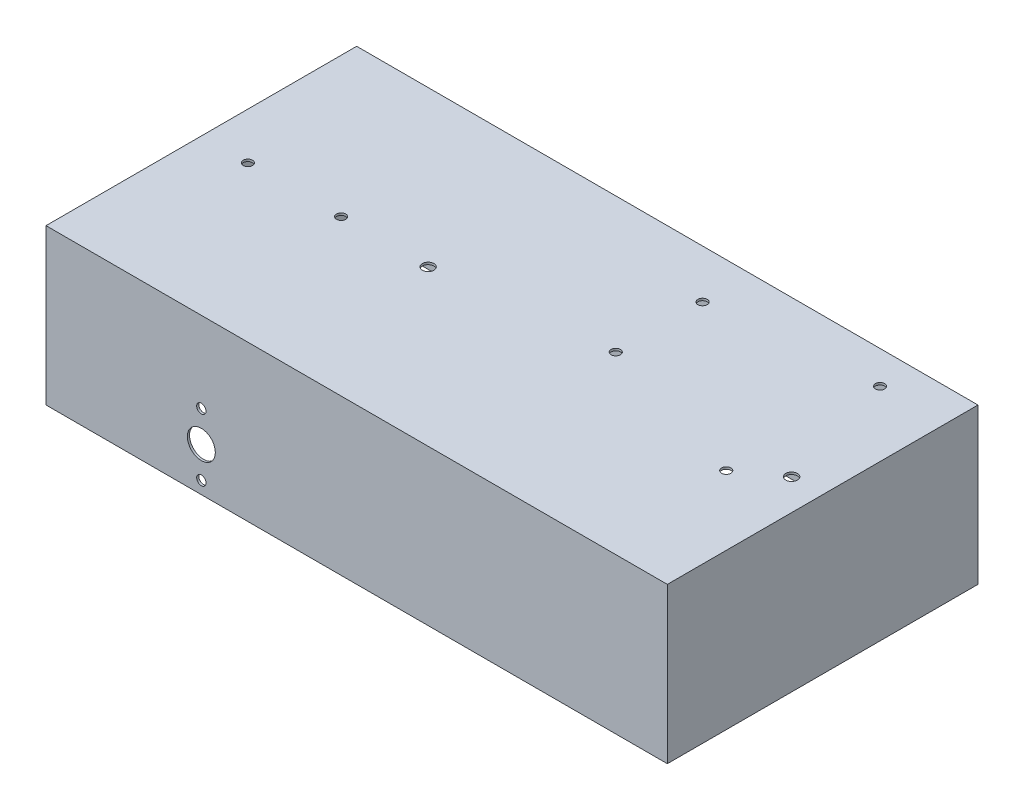
SolidWorks part; units mm, degrees
ref_plane "Front Plane" through (0, 0, 0) normal (0, 0, 1) x (1, 0, 0)
ref_plane "Top Plane" through (0, 0, 0) normal (0, 1, 0) x (1, 0, 0)
ref_plane "Right Plane" through (0, 0, 0) normal (1, 0, 0) x (0, 0, -1)
sketch "Sketch1" plane through (0, 0, 0) normal (0, 1, 0) x (1, 0, 0)
  line L1 (0, 50) -> (200, 50)
  line L2 (0, 50) -> (0, -50)
  line L3 (0, -50) -> (200, -50)
  line L4 (200, 50) -> (200, -50)
  point P4 (0, 0)
  dimension "D1" = 200
  dimension "D2" = 100
extrude "Boss-Extrude1" add sketch "Sketch1" along normal blind 50
sketch "Sketch2" plane through (0, 0, 50) normal (0, 0, 1) x (1, 0, 0)
  line L0 (0, 50) -> (0, 0) construction
  line L1 (50, 24) -> (50, 4) construction
  line L2 (0, 50) -> (200, 50) construction
  circle A0 centre (50, 14) radius 4.5
  circle A1 centre (50, 4) radius 1.5
  circle A2 centre (50, 24) radius 1.5
  point P0 (50, 14)
  point P9 (50, 14)
  dimension "D3" = 9
  dimension "D4" = 3
  dimension "D1" = 50
  dimension "D2" = 36
  dimension "D5" = 20
sketch "Sketch3" plane through (0, 0, 0) normal (0, -1, 0) x (1, 0, 0)
  line L0 (0.7, 49.3) -> (0.7, -49.3)
  line L1 (0.7, -49.3) -> (199.3, -49.3)
  line L2 (199.3, -49.3) -> (199.3, 49.3)
  line L3 (199.3, 49.3) -> (0.7, 49.3)
  line L4 (0, 50) -> (0, -50)
  line L5 (0, -50) -> (200, -50)
  line L6 (200, -50) -> (200, 50)
  line L7 (200, 50) -> (0, 50)
  line L8 (0, 50) -> (0, -50) construction
  line L9 (0, -50) -> (200, -50) construction
  line L10 (200, -50) -> (200, 50) construction
  line L11 (200, 50) -> (0, 50) construction
  dimension "D1" = 0
  dimension "D2" = 0.7
extrude "Cut-Extrude1" cut sketch "Sketch3" against normal offset from surface (49.3 mm away) 0.7 up to face at (100, 50, 0)
sketch "Sketch4" plane through (0, 0, 0) normal (0, -1, 0) x (1, 0, 0)
  line L0 (0.7, -49.3) -> (199.3, -49.3) construction
  line L1 (145, -49.3) -> (199.3, -49.3)
  line L2 (145, -49.3) -> (145, 49.3)
  line L3 (145, 49.3) -> (199.3, 49.3)
  line L4 (199.3, -49.3) -> (199.3, 49.3)
  line L5 (199.3, 49.3) -> (0.7, 49.3) construction
  line L6 (160, -47.9) -> (160, 49.3) construction
  line L7 (200, -50) -> (200, 50) construction
  line L8 (199.3, -49.3) -> (199.3, 49.3) construction
  circle A0 centre (160, 0.7) radius 11.43 construction
  point P12 (160, 0.7)
  dimension "D3" = 22.86
  dimension "D1" = 40
  dimension "D2" = 55
  dimension "D4" = 50
extrude "Boss-Extrude2" add sketch "Sketch4" against normal blind 0.7
extrude "Cut-Extrude2" cut sketch "Sketch2" against normal through all
sketch "Sketch6" plane through (0, 0, 50) normal (0, 0, 1) x (1, 0, 0)
  line L0 (4.6, 50) -> (4.6, 0) construction
  line L1 (0, 50) -> (200, 50) construction
  line L2 (200, 0) -> (0, 0) construction
  line L3 (0, 45) -> (200, 45) construction
  line L4 (0, 50) -> (0, 0) construction
  line L5 (200, 50) -> (200, 0) construction
  line L6 (0, 35) -> (200, 35) construction
  line L7 (54.1, 45) -> (54.1, 35) construction
  line L8 (69.1, 45) -> (69.1, 35) construction
  circle A0 centre (4.6, 45) radius 1.5
  circle A1 centre (4.6, 35) radius 1.5
  circle A2 centre (54.1, 45) radius 1.5
  circle A3 centre (54.1, 35) radius 1.5
  circle A4 centre (69.1, 45) radius 1.5
  circle A5 centre (69.1, 35) radius 1.5
  dimension "D1" = 3
  dimension "D3" = 5
  dimension "D4" = 10
  dimension "D5" = 4.6
  dimension "D6" = 15
  dimension "D7" = 54.1
extrude "Cut-Extrude3" [suppressed] cut sketch "Sketch6" against normal up to surface (0.7 mm away) up to face at (51.5, 4, 49.3)
sketch "Sketch7" plane through (0, 0, 0) normal (-1, 0, 0) x (0, 0, 1)
  line L0 (42, 50) -> (42, 0) construction
  line L1 (-50, 50) -> (50, 50) construction
  line L2 (-50, 0) -> (50, 0) construction
  circle A0 centre (42, 45) radius 1.5
  circle A1 centre (42, 35) radius 1.5
  dimension "D4" = 3
  dimension "D1" = 8
  dimension "D2" = 5
  dimension "D3" = 10
extrude "Cut-Extrude4" [suppressed] cut sketch "Sketch7" against normal up to surface (0.7 mm away) up to face at (0.7, 24.65, 0)
sketch "Sketch8" plane through (0, 0, 0) normal (0, -1, 0) x (1, 0, 0)
  line L0 (160, -47.9) -> (160, 49.3) construction
  circle A0 centre (160, 8.45) radius 1.21
  circle A1 centre (160, -7.05) radius 1.21
  dimension "D2" = 2.42
  dimension "D1" = 7.75
  dimension "D3" = 7.75
extrude "Cut-Extrude6" cut sketch "Sketch8" against normal blind 1.8 contours A1 | A0
sketch "Sketch9" plane through (0, 50, 0) normal (0, 1, 0) x (1, 0, 0)
  line L0 (0, 0) -> (200, 0) construction
  line L1 (200, 50) -> (200, -50) construction
  circle A0 centre (15, 0) radius 1.5
  circle A1 centre (45, 0) radius 1.5
  dimension "D1" = 3
  dimension "D2" = 15
  dimension "D3" = 30
sketch "Sketch10" plane through (0, 49.3, 0) normal (0, -1, 0) x (1, 0, 0)
  line L0 (0, 0) -> (200, 0)
  line L1 (200, -50) -> (200, 50) construction
  circle A0 centre (190, 0) radius 1.87
  circle A1 centre (73, 0) radius 1.87
  dimension "D2" = 3.74
  dimension "D1" = 117
  dimension "D3" = 10
extrude "Cut-Extrude8" cut sketch "Sketch10" against normal up to surface (0.7 mm away) contours A0 | A1 up to face at (100, 50, 0)
extrude "Cut-Extrude7" cut sketch "Sketch9" against normal through all
sketch "Sketch11" plane through (0, 50, 0) normal (0, 1, 0) x (1, 0, 0)
  line L0 (193, 50) -> (193, -50) construction
  line L1 (0, 50) -> (200, 50) construction
  line L2 (200, -50) -> (0, -50) construction
  line L3 (200, 42) -> (0, 42) construction
  line L4 (200, 50) -> (200, -50) construction
  line L5 (0, -50) -> (0, 50) construction
  line L6 (126.96, 6.44) -> (126.96, 34.38) construction
  circle A0 centre (126.96, 34.38) radius 1.5
  circle A1 centre (179.03, 39.46) radius 1.5
  circle A2 centre (177.76, -8.8) radius 1.5
  circle A3 centre (126.96, 6.44) radius 1.5
  point P12 (193, 42)
  dimension "D8" = 3
  dimension "D1" = 13.97
  dimension "D2" = 66.04
  dimension "D3" = 15.24
  dimension "D4" = 2.54
  dimension "D5" = 7.62
  dimension "D6" = 50.8
  dimension "D7" = 35.56
  dimension "D9" = 7
  dimension "D10" = 8
extrude "Cut-Extrude9" cut sketch "Sketch11" against normal up to surface (0.7 mm away) up to face at (15, 49.3, 1.5)
